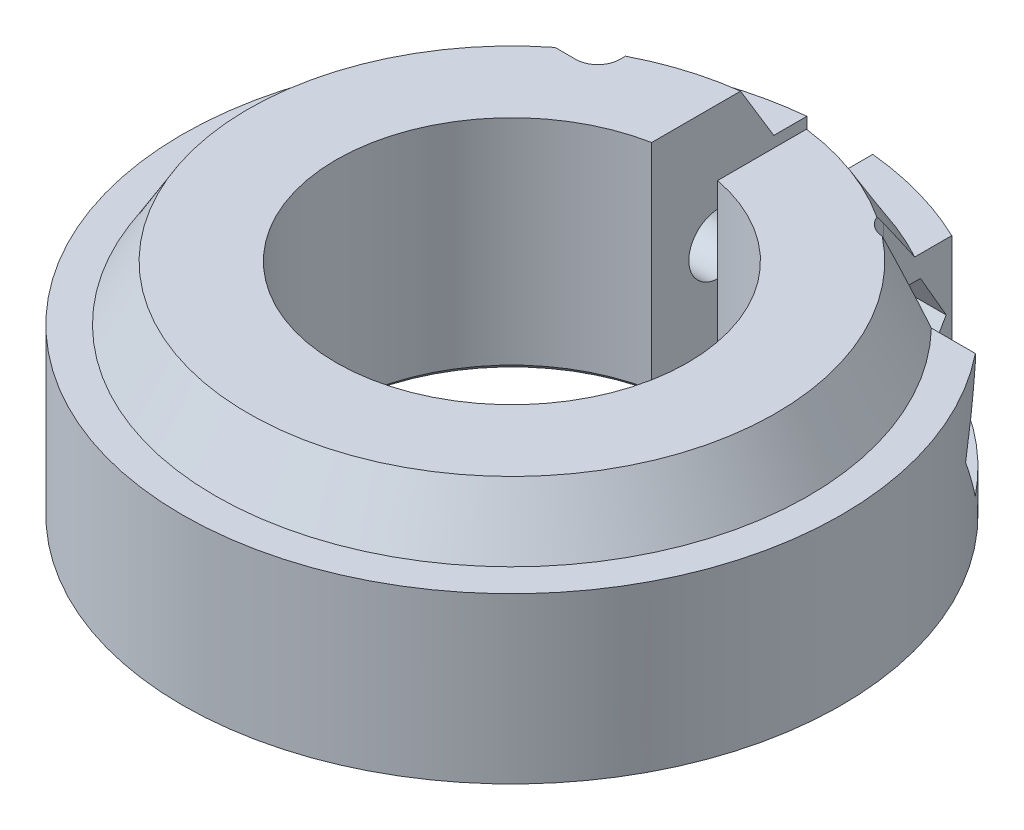
SolidWorks part; units mm, degrees
ref_plane "Front Plane" through (0, 0, 0) normal (0, 0, 1) x (1, 0, 0)
ref_plane "Top Plane" through (0, 0, 0) normal (0, 1, 0) x (1, 0, 0)
ref_plane "Right Plane" through (0, 0, 0) normal (1, 0, 0) x (0, 0, -1)
sketch "Sketch1" plane through (0, 0, 0) normal (0, 0, 1) x (1, 0, 0)
  line L0 (16, 0) -> (16, 20)
  line L1 (16, 20) -> (24, 20)
  line L2 (24, 20) -> (27, 15)
  line L3 (27, 15) -> (30, 15)
  line L4 (30, 15) -> (30, 0)
  line L5 (30, 0) -> (16, 0)
  line L6 (0, 0) -> (0, 31.75) construction
  dimension "D1" = 32
  dimension "D2" = 60
  dimension "D3" = 20
  dimension "D5" = 15
  dimension "D6" = 8
  dimension "D7" = 54
revolve "Revolve1" add sketch "Sketch1" angle 360 about L6
sketch "Sketch2" plane through (0, 0, 0) normal (0, -1, 0) x (1, 0, 0)
  line L0 (0, 0) -> (44.9434, 0) construction
  line L1 (0, 0) -> (0, 10.8197) construction
  line L3 (-3, 0) -> (3, 0)
  line L4 (-3, 0) -> (-3, -50)
  line L5 (-3, -50) -> (3, -50)
  line L6 (3, 0) -> (3, -50)
  circle A0 centre (34.25, 0) radius 2.5 construction
  dimension "D1" = 5
  dimension "D2" = 34.25
  dimension "D3" = 50
  dimension "D4" = 6
extrude "Cut-Extrude1" cut sketch "Sketch2" against normal through all
sketch "Sketch4" plane through (3, 0, 0) normal (-1, 0, 0) x (0, 0, 1)
  line L0 (-29.8496, 0) -> (-15.7162, 0) construction
  line L2 (-21.8496, 9) -> (-85.6031, 9) construction
  line L5 (-29.8496, 15) -> (-29.8496, 0) construction
  circle A0 centre (-21.8496, 9) radius 2.75
  dimension "D1" = 5.5
  dimension "D2" = 8
  dimension "D3" = 9
extrude "Cut-Extrude2" cut sketch "Sketch4" against normal through all and the other way through all
ref_plane "Plane1" through (13, 0, 0) normal (-1, 0, 0) x (0, 0, 1)
ref_plane "Plane2" through (-11, 0, 0) normal (1, 0, 0) x (0, 0, -1)
sketch "Sketch5" plane through (-11, 0, 0) normal (1, 0, 0) x (0, 0, -1)
  line L0 (18.8185, 14.25) -> (18.8185, 43.5)
  line L1 (18.8185, 3.75) -> (24.8807, 3.75)
  line L2 (24.8807, 3.75) -> (27.9118, 9) construction
  line L3 (27.9118, 9) -> (24.8807, 14.25) construction
  line L4 (24.8807, 14.25) -> (18.8185, 14.25) construction
  line L5 (18.8185, 14.25) -> (15.7874, 9)
  line L6 (15.7874, 9) -> (18.8185, 3.75)
  line L7 (18.8185, 43.5) -> (31.8185, 43.5)
  line L8 (24.8807, 3.75) -> (31.8185, 3.75)
  line L9 (31.8185, 3.75) -> (31.8185, 43.5)
  circle A0 centre (21.8496, 9) radius 5.25 construction
  dimension "D1" = 10.5
  dimension "D2" = 13
  dimension "D3" = 39.75
extrude "Cut-Extrude3" cut sketch "Sketch5" against normal through all
sketch "Sketch6" plane through (13, 0, 0) normal (-1, 0, 0) x (0, 0, 1)
  line L1 (-24.8807, 3.75) -> (-18.8185, 3.75)
  line L2 (-18.8185, 3.75) -> (-15.7874, 9)
  line L3 (-15.7874, 9) -> (-18.8185, 14.25)
  line L4 (-18.8185, 14.25) -> (-24.8807, 14.25) construction
  line L5 (-24.8807, 14.25) -> (-27.9118, 9) construction
  line L6 (-27.9118, 9) -> (-24.8807, 3.75) construction
  line L7 (-18.8185, 23.75) -> (-31.8185, 23.75)
  line L8 (-31.8185, 23.75) -> (-31.8185, 3.75)
  line L9 (-31.8185, 3.75) -> (-24.8807, 3.75)
  line L10 (-18.8185, 14.25) -> (-18.8185, 23.75)
  circle A0 centre (-21.8496, 9) radius 5.25 construction
  dimension "D1" = 10.5
  dimension "D2" = 13
  dimension "D3" = 20
extrude "Cut-Extrude4" cut sketch "Sketch6" against normal through all
sketch "Sketch8" plane through (13, 0, 0) normal (1, 0, 0) x (0, 0, -1)
  line L1 (24.1879, 4.95) -> (26.5262, 9)
  line L2 (26.5262, 9) -> (24.1879, 13.05)
  line L3 (24.1879, 13.05) -> (19.5114, 13.05)
  line L4 (19.5114, 13.05) -> (17.1731, 9)
  line L5 (17.1731, 9) -> (19.5114, 4.95)
  line L6 (19.5114, 4.95) -> (24.1879, 4.95)
  circle A0 centre (21.8496, 9) radius 4.05 construction
  dimension "D1" = 8.1
extrude "Cut-Extrude5" cut sketch "Sketch8" against normal blind 4
chamfer "Chamfer1" distance 0.5 angle 45 1 edges at (0, 0, 16)
fillet "Fillet1" radius 2 2 edges at (13, 17.125, -18.8185) (-11, 17.125, -18.8185)
